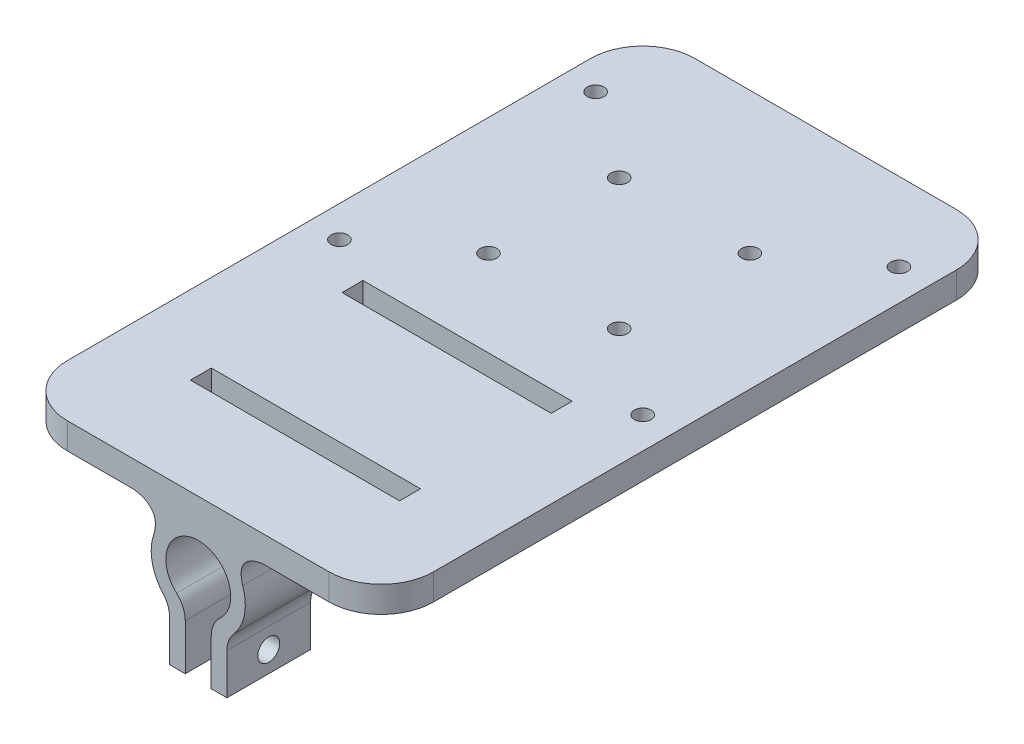
SolidWorks part; units mm, degrees
ref_plane "Front Plane" through (0, 0, 0) normal (0, 0, 1) x (1, 0, 0)
ref_plane "Top Plane" through (0, 0, 0) normal (0, 1, 0) x (1, 0, 0)
ref_plane "Right Plane" through (0, 0, 0) normal (1, 0, 0) x (0, 0, -1)
sketch "Sketch3" plane through (0, 0, 0) normal (0, 0, 1) x (1, 0, 0)
  line L0 (0, 11) -> (0, 0) construction
  line L1 (-35, 13.5) -> (35, 13.5)
  line L2 (-35, 13.5) -> (-35, 8.5)
  line L3 (-35, 8.5) -> (35, 8.5)
  line L4 (35, 13.5) -> (35, 8.5)
  line L5 (-35, 13.5) -> (35, 8.5) construction
  line L6 (-35, 8.5) -> (35, 13.5) construction
  point P0 (0, 11)
  dimension "D1" = 5
  dimension "D2" = 70
  dimension "D3" = 11
extrude "Boss-Extrude2" add sketch "Sketch3" along normal blind 120 from offset 10
sketch "Sketch1" plane through (0, 0, 0) normal (0, 0, 1) x (1, 0, 0)
  line L0 (-35, 8.5) -> (35, 8.5) construction
  line L1 (0, 0) -> (0, -9) construction
  line L2 (-12.3518, 8.5) -> (12.3518, 8.5)
  line L3 (0, 0) -> (-5.4853, -7.1352) construction
  line L5 (2.4853, -17.1352) -> (2.4853, -8.3313)
  line L6 (-3.9853, -17.1352) -> (-2.4853, -17.1352)
  line L7 (-3.9853, -17.1352) -> (-5.4853, -17.1352)
  line L8 (-2.4853, -17.1352) -> (-2.4853, -8.3313)
  line L9 (-5.4853, -17.1352) -> (-5.4853, -9.2768)
  line L10 (3.9853, -17.1352) -> (5.4853, -17.1352)
  line L11 (3.9853, -17.1352) -> (2.4853, -17.1352)
  line L12 (5.4853, -17.1352) -> (5.4853, -9.2768)
  arc A0 (4.1436, -4.612) -> (-4.1436, -4.612) centre (0, 0) ccw
  arc A1 (6.7405, -5.9637) -> (8.4982, 2.9632) centre (0, 0) ccw
  arc A2 (-5.4853, -9.2768) -> (-6.7405, -5.9637) centre (-10.4853, -9.2768) ccw
  arc A3 (-2.4853, -8.3313) -> (-4.1436, -4.612) centre (-7.4853, -8.3313) ccw
  arc A4 (2.4853, -8.3313) -> (4.1436, -4.612) centre (7.4853, -8.3313) cw
  arc A5 (5.4853, -9.2768) -> (6.7405, -5.9637) centre (10.4853, -9.2768) cw
  arc A6 (-8.4982, 2.9632) -> (-6.7405, -5.9637) centre (0, 0) ccw
  spline S0 degree 3 poles (-12.3518, 8.5) (-9.9792, 8.1529) (-7.3004, 7.013) (-8.4982, 2.9632) knots 0 0 0 0 1 1 1 1
  spline S1 degree 3 poles (12.3518, 8.5) (9.9792, 8.1529) (7.3004, 7.013) (8.4982, 2.9632) knots 0 0 0 0 1 1 1 1
  point P18 (-2.4853, -5.6801)
  point P21 (2.4853, -5.6801)
  point P24 (5.4853, -7.1352)
  dimension "D1" = 12.4
  dimension "D2" = 18
  dimension "D6" = 1.5
  dimension "D3" = 5
  dimension "D4" = 5
  dimension "D10" = 5
  dimension "D11" = 5
  dimension "D5" = 37.552
  dimension "D7" = 1.5
  dimension "D8" = 10
  dimension "D9" = 11.4552
extrude "Boss-Extrude3" add sketch "Sketch1" along normal blind 8 and the other way blind 8 from offset 18
ref_plane "Plane4" through (0, 0, 70) normal (0, 0, 1) x (1, 0, 0)
sketch "Sketch4" plane through (-5.4853, 0, 0) normal (-1, 0, 0) x (0, 0, 1)
  line L0 (10, -9.2768) -> (26, -16.9992) construction
  line L1 (26, -9.2768) -> (26, -17.1352) construction
  circle A0 centre (18, -13.138) radius 2.1
  dimension "D1" = 4.2
extrude "Cut-Extrude1" cut sketch "Sketch4" against normal blind 11
mirror "Mirror2" about plane through (0, 0, 70) normal (0, 0, 1) of "Boss-Extrude3", "Cut-Extrude1"
sketch "Sketch5" plane through (0, 13.5, 0) normal (0, 1, 0) x (1, 0, 0)
  line L0 (-2.75, -70) -> (2.75, -70) construction
  line L1 (-29, -25) -> (29, -25) construction
  line L2 (-29, -25) -> (-29, -74) construction
  line L3 (-29, -74) -> (29, -74) construction
  line L4 (29, -25) -> (29, -74) construction
  line L5 (-29, -25) -> (29, -74) construction
  line L6 (-29, -74) -> (29, -25) construction
  line L8 (35, -10) -> (-35, -130) construction
  line L9 (-35, -10) -> (-35, -130) construction
  line L10 (35, -130) -> (-35, -130) construction
  line L11 (35, -10) -> (-35, -10) construction
  line L14 (35, -130) -> (35, -10) construction
  circle A0 centre (29, -25) radius 1.6
  circle A1 centre (29, -74) radius 1.6
  circle A2 centre (-29, -74) radius 1.6
  circle A3 centre (-29, -25) radius 1.6
  point P0 (0, -70)
  point P11 (0, 0)
  point P23 (0, -49.5)
  dimension "D3" = 3.2
  dimension "D4" = 15
  dimension "D1" = 58
  dimension "D2" = 49
  dimension "D5" = 6
sketch "Sketch6" plane through (0, 13.5, 0) normal (0, 1, 0) x (1, 0, 0)
  line L0 (-16.8494, -70) -> (16.8494, -70) construction
  line L1 (-20, -82.5) -> (20, -82.5)
  line L2 (-20, -82.5) -> (-20, -107.5) construction
  line L3 (-20, -107.5) -> (20, -107.5)
  line L4 (20, -82.5) -> (20, -107.5) construction
  line L5 (-20, -82.5) -> (20, -107.5) construction
  line L6 (-20, -107.5) -> (20, -82.5) construction
  line L9 (-20, -82.5) -> (-20, -78.5)
  line L10 (-20, -78.5) -> (20, -78.5)
  line L11 (20, -78.5) -> (20, -89.585)
  line L12 (-20, -107.5) -> (-20, -111.5)
  line L13 (-20, -111.5) -> (20, -111.5)
  line L14 (20, -111.5) -> (20, -107.5)
  line L15 (20, -82.5) -> (20, -89.585)
  point P0 (0, -95)
  dimension "D1" = 25
  dimension "D2" = 40
  dimension "D3" = 25
  dimension "D5" = 4
  dimension "D6" = 4
sketch "Sketch7" plane through (0, 13.5, 0) normal (0, 1, 0) x (1, 0, 0)
  line L0 (0, -10) -> (0, -130) construction
  line L1 (-12.5, -37) -> (12.5, -37) construction
  line L2 (-12.5, -37) -> (-12.5, -62) construction
  line L3 (-12.5, -62) -> (12.5, -62) construction
  line L4 (12.5, -37) -> (12.5, -62) construction
  line L5 (-12.5, -37) -> (12.5, -62) construction
  line L6 (-12.5, -62) -> (12.5, -37) construction
  line L7 (35, -10) -> (-35, -10) construction
  line L8 (35, -130) -> (-35, -130) construction
  circle A0 centre (12.5, -37) radius 1.6
  circle A1 centre (12.5, -62) radius 1.6
  circle A2 centre (-12.5, -62) radius 1.6
  circle A3 centre (-12.5, -37) radius 1.6
  point P0 (0, -70)
  point P12 (0, -49.5)
  dimension "D4" = 3.2
  dimension "D1" = 25
  dimension "D2" = 25
fillet "Fillet1" radius 10 4 edges at (35, 11, 10) (35, 11, 130) (-35, 11, 130) (-35, 11, 10)
extrude "Cut-Extrude2" cut sketch "Sketch5" against normal blind 11
extrude "Cut-Extrude5" cut sketch "Sketch7" against normal up to next
extrude "Cut-Extrude6" cut sketch "Sketch6" against normal up to next contours L11 L10 L9 L1 | L13 L14 L3 L12 region at (0, 13.5, 80.5) region at (0, 13.5, 109.5)
